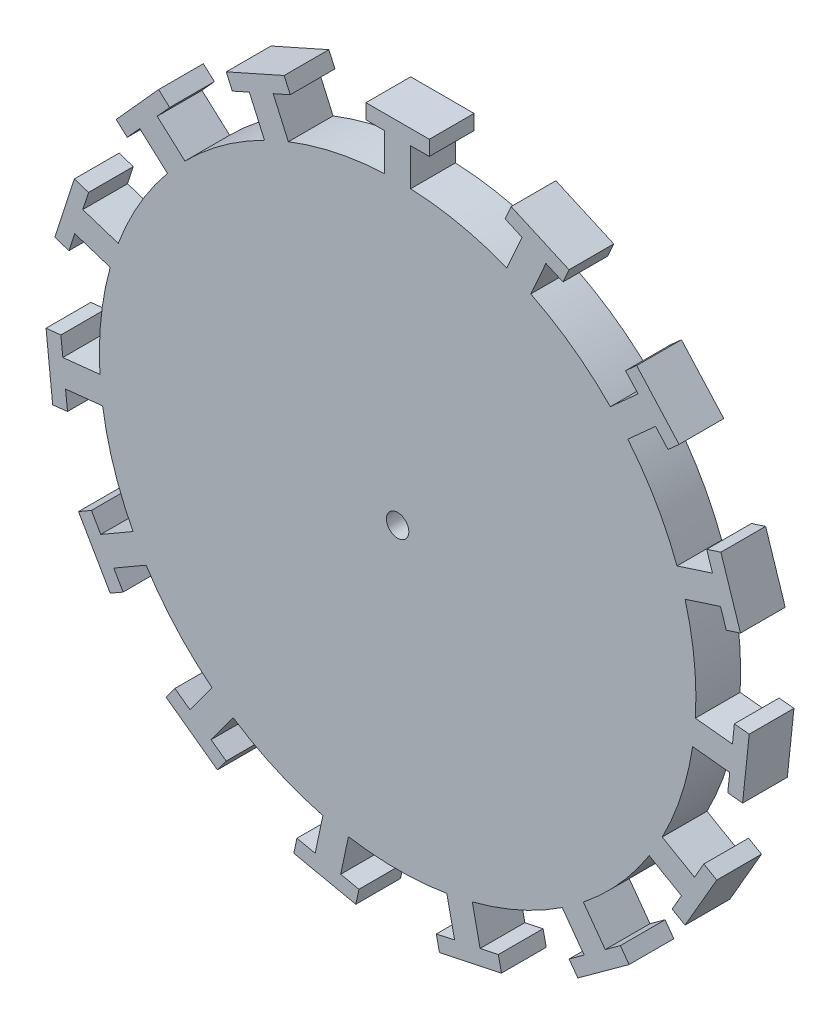
SolidWorks part; units mm, degrees
ref_plane "Front Plane" through (0, 0, 0) normal (0, 0, 1) x (1, 0, 0)
ref_plane "Top Plane" through (0, 0, 0) normal (0, 1, 0) x (1, 0, 0)
ref_plane "Right Plane" through (0, 0, 0) normal (1, 0, 0) x (0, 0, -1)
sketch "Sketch1" plane through (0, 0, 0) normal (0, 0, 1) x (1, 0, 0)
  circle A0 centre (0, 0) radius 40
  dimension "D1" = 80
extrude "Boss-Extrude1" add sketch "Sketch1" along normal blind 2
sketch "Sketch6" plane through (0, 0, 0) normal (0, 0, 1) x (1, 0, 0)
  line L0 (-1.75, 39.9617) -> (-1.75, 44.9617)
  line L1 (0, 37.6165) -> (0, 55.5597) construction
  line L2 (1.75, 39.9617) -> (1.75, 44.9617)
  line L3 (-1.75, 44.9617) -> (-4.25, 44.9617)
  line L4 (-4.25, 44.9617) -> (-4.25, 46.9617)
  line L5 (-4.25, 46.9617) -> (4.25, 46.9617)
  line L6 (4.25, 46.9617) -> (4.25, 44.9617)
  line L7 (4.25, 44.9617) -> (1.75, 44.9617)
  circle A0 centre (0, 0) radius 40 construction
  circle A2 centre (0, 0) radius 40
  arc A3 (-1.75, 39.9617) -> (1.75, 39.9617) centre (0, 0) ccw
  dimension "D1" = 3.5
  dimension "D2" = 5
  dimension "D3" = 2
  dimension "D4" = 2.5
  dimension "D5" = 0
extrude "Boss-Extrude2" add sketch "Sketch6" along normal blind 6
pattern_circular "CirPattern1" count 15 over 360 about axis through (0, 0, 6) along (0, 0, 1) of "Boss-Extrude2"
sketch "Sketch7" plane through (0, 0, 6) normal (0, 0, 1) x (1, 0, 0)
  circle A0 centre (0, 0) radius 1.5
  dimension "D1" = 3
extrude "Cut-Extrude1" cut sketch "Sketch7" against normal blind 10
equation "\"diameter\"=80"
equation "\"D1\" = \"diameter\" / 2"
